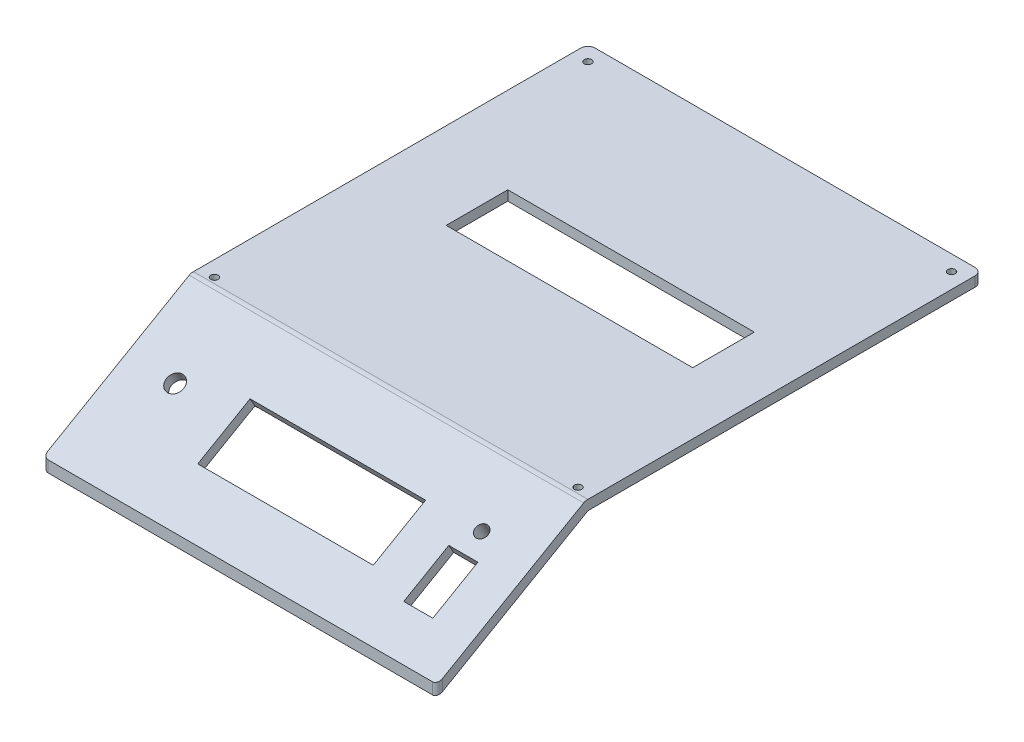
SolidWorks part; units mm, degrees
ref_plane "Front Plane" through (0, 0, 0) normal (0, 0, 1) x (1, 0, 0)
ref_plane "Top Plane" through (0, 0, 0) normal (0, 1, 0) x (1, 0, 0)
ref_plane "Right Plane" through (0, 0, 0) normal (1, 0, 0) x (0, 0, -1)
sketch "Sketch1" plane through (0, 0, 0) normal (0, 1, 0) x (1, 0, 0)
  line L1 (-80, 80) -> (80, 80)
  line L2 (-80, 80) -> (-80, -80)
  line L3 (-80, -80) -> (80, -80)
  line L4 (80, 80) -> (80, -80)
  circle A0 centre (-73.75, 73.75) radius 1.5
  circle A1 centre (73.75, 73.75) radius 1.5
  circle A2 centre (-73.75, -77.75) radius 1.5
  circle A3 centre (73.75, -77.75) radius 1.5
  dimension "D5" = 3
  dimension "D6" = 6.25
  dimension "D8" = 3
  dimension "D11" = 3
  dimension "D16" = 3
  dimension "D1" = 160
  dimension "D2" = 160
  dimension "D3" = 80
  dimension "D4" = 80
  dimension "D7" = 6.25
  dimension "D9" = 6.25
  dimension "D10" = 6.25
  dimension "D12" = 2.25
  dimension "D13" = 6.25
  dimension "D14" = 6.25
  dimension "D15" = 2.25
extrude "Boss-Extrude1" add sketch "Sketch1" along normal blind 4
ref_plane "Plane1" through (0, 34.641, 20) normal (0, 0.866, 0.5) x (1, 0, 0)
sketch "Sketch5" plane through (0, 34.641, 20) normal (0, 0.866, 0.5) x (1, 0, 0)
  line L0 (-80, -67.282) -> (80, -67.282)
  line L1 (-80, -67.282) -> (80, -67.282) construction
  line L2 (80, -67.282) -> (80, -142.282)
  line L3 (80, -142.282) -> (-80, -142.282)
  line L4 (-80, -142.282) -> (-80, -67.282)
  dimension "D1" = 160
  dimension "D2" = 75
extrude "Boss-Extrude4" add sketch "Sketch5" along normal blind 4
fillet "Fillet1" radius 3 1 edges at (0, 4.4641, 80.2679)
fillet "Fillet2" radius 3 1 edges at (80, 2, -80)
fillet "Fillet3" radius 3 1 edges at (-80, 2, -80)
sketch "Sketch12" plane through (80, 0, 0) normal (1, 0, 0) x (0, 0, -1)
  line L0 (-145.2199, -33.0359) -> (-143.2199, -36.5)
  line L1 (-145.2199, -33.0359) -> (-143.2199, -36.5) construction
  line L3 (-141.0028, -35.22) -> (-141.0028, -30.6012)
  line L5 (48.5827, 74.2372) -> (-88.5827, -4.9552) construction
  line L6 (-143.2199, -36.5) -> (-141.0028, -35.22)
  line L9 (-141.0028, -30.6012) -> (-145.2199, -33.0359)
  dimension "D1" = 2.56
extrude "Cut-Extrude6" cut sketch "Sketch12" against normal blind 165
fillet "Fillet8" radius 2 1 edges at (80, -32.9106, 141.0028)
fillet "Fillet9" radius 2 1 edges at (-80, -32.9106, 141.0028)
sketch "Sketch13" plane through (0, 4, 0) normal (0, 1, 0) x (1, 0, 0)
  line L1 (-45, 12.5) -> (55, 12.5)
  line L2 (-45, 12.5) -> (-45, -12.5)
  line L3 (-45, -12.5) -> (55, -12.5)
  line L4 (55, 12.5) -> (55, -12.5)
  dimension "D1" = 100
  dimension "D2" = 25
  dimension "D3" = 55
  dimension "D4" = 12.5
extrude "Cut-Extrude7" cut sketch "Sketch13" against normal blind 10
sketch "Sketch17" plane through (0, 38.1051, 22) normal (0, 0.866, 0.5) x (1, 0, 0)
  line L0 (80, -68.9932) -> (-80, -68.9932) construction
  line L4 (-80, -68.9932) -> (-80, -135.1032) construction
  line L7 (-35.6, -91.7432) -> (35.6, -91.7432)
  line L8 (-35.6, -91.7432) -> (-35.6, -116.2432)
  line L9 (-35.6, -116.2432) -> (35.6, -116.2432)
  line L10 (35.6, -91.7432) -> (35.6, -116.2432)
  dimension "D1" = 71.2
  dimension "D2" = 24.5
  dimension "D3" = 44.4
  dimension "D4" = 22.75
extrude "Cut-Extrude10" cut sketch "Sketch17" against normal blind 10
sketch "Sketch20" plane through (0, 34.641, 20) normal (0, -0.866, -0.5) x (1, 0, 0)
  circle A0 centre (-37.5924, 119.5019) radius 2.5
  circle A3 centre (37.5676, 88.5019) radius 2.5
  circle A4 centre (37.5676, 119.5019) radius 2.5
  circle A5 centre (-37.5924, 88.5019) radius 2.5
  dimension "D5" = 5
  dimension "D6" = 31
  dimension "D1" = 75.16
  dimension "D2" = 75.16
  dimension "D3" = 2
  dimension "D4" = 2
  dimension "D7" = 31
extrude "Boss-Extrude5" add sketch "Sketch20" along normal blind 3.2
sketch "Sketch21" plane through (0, 38.1051, 22) normal (0, 0.866, 0.5) x (1, 0, 0)
  line L5 (52.0971, -99.9292) -> (63.8971, -99.9292)
  line L6 (52.0971, -99.9292) -> (52.0971, -121.0292)
  line L7 (52.0971, -121.0292) -> (63.8971, -121.0292)
  line L8 (63.8971, -99.9292) -> (63.8971, -121.0292)
  dimension "D1" = 21.1
  dimension "D2" = 11.8
extrude "Cut-Extrude11" cut sketch "Sketch21" against normal blind 5
sketch "Sketch23" plane through (0, 38.1051, 22) normal (0, 0.866, 0.5) x (1, 0, 0)
  line L0 (63.8971, -99.9292) -> (52.0971, -99.9292) construction
  circle A0 centre (58.0971, -91.4292) radius 2.55
  dimension "D1" = 5.1
  dimension "D2" = 8.5
  dimension "D3" = 5.8
extrude "Cut-Extrude12" cut sketch "Sketch23" against normal blind 4
sketch "Sketch24" plane through (0, 34.641, 20) normal (0, -0.866, -0.5) x (1, 0, 0)
  circle A0 centre (58.0971, 91.4292) radius 4
  dimension "D1" = 8
extrude "Boss-Extrude6" add sketch "Sketch24" along normal blind 4
sketch "Sketch25" plane through (0, 34.641, 20) normal (0, -0.866, -0.5) x (1, 0, 0)
  circle A0 centre (58.0971, 91.4292) radius 2.55
  dimension "D1" = 5.1
extrude "Cut-Extrude15" cut sketch "Sketch25" along normal blind 4
sketch "Sketch26" plane through (0, 38.1051, 22) normal (0, 0.866, 0.5) x (1, 0, 0)
  line L0 (-78, -137.4126) -> (78, -137.4126) construction
  line L1 (-80, -68.9932) -> (-80, -135.1032) construction
  circle A0 centre (-59.8, -98.9126) radius 3.5
  dimension "D1" = 38.5
  dimension "D2" = 7
  dimension "D3" = 20.2
extrude "Cut-Extrude16" cut sketch "Sketch26" against normal blind 10
